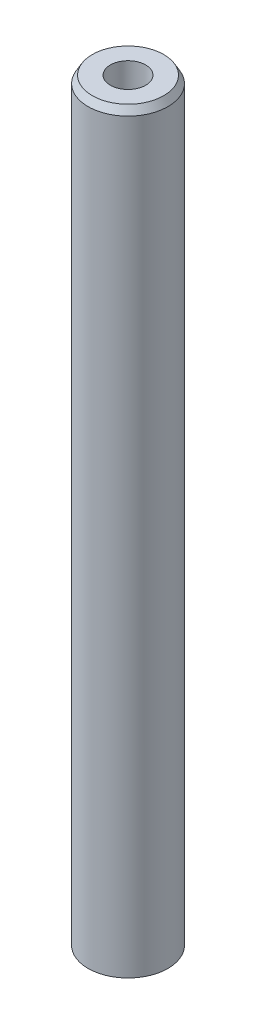
SolidWorks part; units mm, degrees
ref_plane "Front Plane" through (0, 0, 0) normal (0, 0, 1) x (1, 0, 0)
ref_plane "Top Plane" through (0, 0, 0) normal (0, 1, 0) x (1, 0, 0)
ref_plane "Right Plane" through (0, 0, 0) normal (1, 0, 0) x (0, 0, -1)
sketch "Sketch1" plane through (0, 0, 0) normal (0, 1, 0) x (1, 0, 0)
  circle A0 centre (0, 0) radius 25
  dimension "SHAFT_OD" = 50
extrude "Boss-Extrude1" add sketch "Sketch1" along normal blind 474.529
sketch "Sketch2" plane through (0, 0, 0) normal (0, 1, 0) x (1, 0, 0)
  circle A0 centre (0, 0) radius 11.0523
  dimension "BORE_D" = 22.1045
extrude "Cut-Extrude1" cut sketch "Sketch2" along normal through all
chamfer "Chamfer1" distance 4.5887 angle 30 2 edges at (0, 474.529, 25) (0, 0, 25) first distance on face at (0, 474.529, 25) first distance on face at (0, 0, 11.0523)
